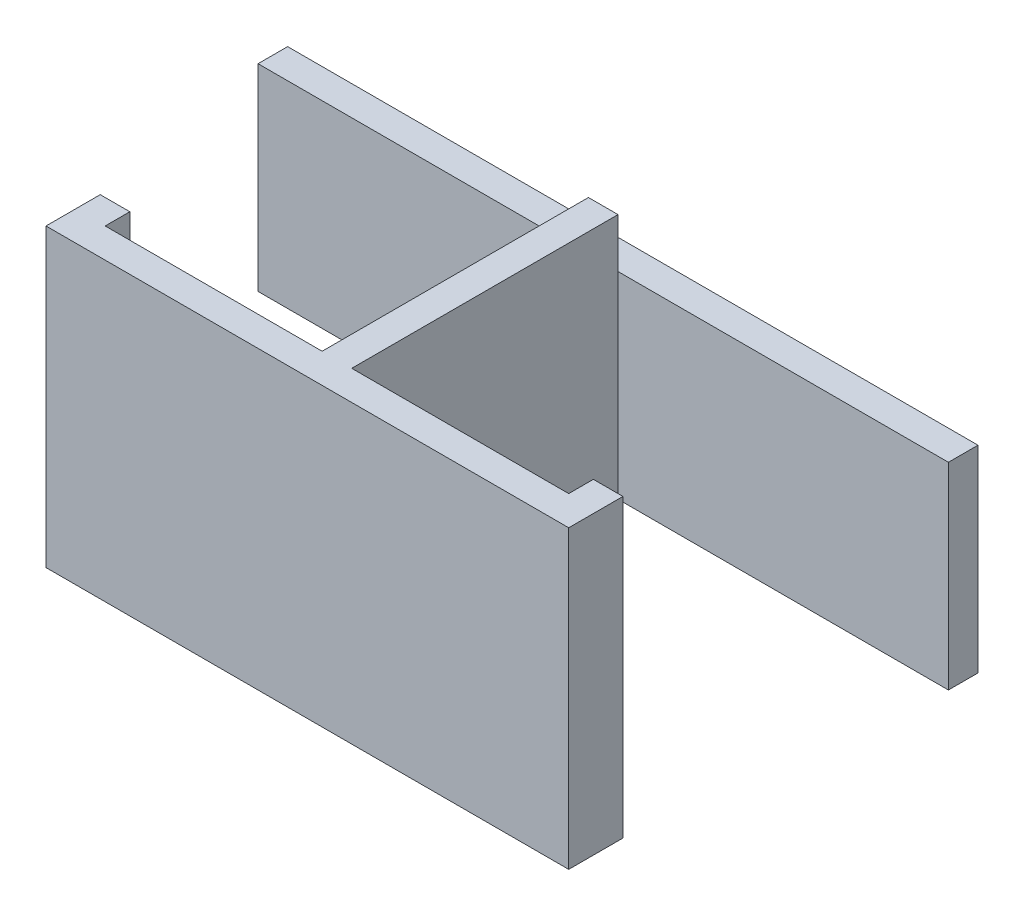
SolidWorks part; units mm, degrees
ref_plane "Front Plane" through (0, 0, 0) normal (0, 0, 1) x (1, 0, 0)
ref_plane "Top Plane" through (0, 0, 0) normal (0, 1, 0) x (1, 0, 0)
ref_plane "Right Plane" through (0, 0, 0) normal (1, 0, 0) x (0, 0, -1)
sketch "Sketch1" plane through (0, 0, 0) normal (0, 0, 1) x (1, 0, 0)
  line L1 (0, 0) -> (-88.9, 0)
  line L2 (0, 0) -> (0, 25.4)
  line L3 (0, 25.4) -> (-88.9, 25.4)
  line L4 (-88.9, 0) -> (-88.9, 25.4)
  dimension "D1" = 25.4
  dimension "D2" = 88.9
extrude "Boss-Extrude1" add sketch "Sketch1" along normal blind 3.81
sketch "Sketch2" plane through (0, 0, 3.81) normal (0, 0, 1) x (1, 0, 0)
  line L0 (-88.9, 0) -> (0, 0) construction
  line L1 (-42.545, -6.35) -> (-46.355, -6.35)
  line L2 (-42.545, -6.35) -> (-42.545, 31.75)
  line L3 (-42.545, 31.75) -> (-46.355, 31.75)
  line L4 (-46.355, -6.35) -> (-46.355, 31.75)
  line L7 (0, 0) -> (0, 25.4) construction
  point P6 (0, 12.7)
  point P7 (-42.545, 12.7)
  point P8 (0, 0)
  point P10 (-44.45, 0)
  point P11 (-44.45, -6.35)
  dimension "D1" = 3.81
  dimension "D2" = 38.1
extrude "Boss-Extrude2" add sketch "Sketch2" along normal blind 38.1
sketch "Sketch3" plane through (-42.545, 0, 0) normal (1, 0, 0) x (0, 0, -1)
  line L0 (-41.91, -6.35) -> (-3.81, -6.35) construction
  line L1 (-41.91, 31.75) -> (-38.1, 31.75)
  line L2 (-41.91, 31.75) -> (-41.91, -6.35)
  line L3 (-41.91, -6.35) -> (-38.1, -6.35)
  line L4 (-38.1, 31.75) -> (-38.1, -6.35)
  line L5 (-41.91, 31.75) -> (-3.81, 31.75) construction
  line L6 (-41.91, -6.35) -> (-41.91, 31.75) construction
  dimension "D1" = 3.81
extrude "Boss-Extrude3" add sketch "Sketch3" along normal blind 31.75
sketch "Sketch4" plane through (0, 0, 38.1) normal (0, 0, -1) x (-1, 0, 0)
  line L0 (10.795, -6.35) -> (42.545, -6.35) construction
  line L1 (10.795, 31.75) -> (14.605, 31.75)
  line L2 (10.795, 31.75) -> (10.795, -6.35)
  line L3 (10.795, -6.35) -> (14.605, -6.35)
  line L4 (14.605, 31.75) -> (14.605, -6.35)
  line L5 (10.795, 31.75) -> (46.355, 31.75) construction
  line L6 (10.795, -6.35) -> (10.795, 31.75) construction
  dimension "D1" = 3.81
extrude "Boss-Extrude4" add sketch "Sketch4" along normal blind 3.175
ref_plane "Plane1" through (-44.45, 0, 0) normal (-1, 0, 0) x (0, 0, 1)
mirror "Mirror2" about plane through (-44.45, 0, 0) normal (-1, 0, 0) of "Boss-Extrude3", "Boss-Extrude4"
